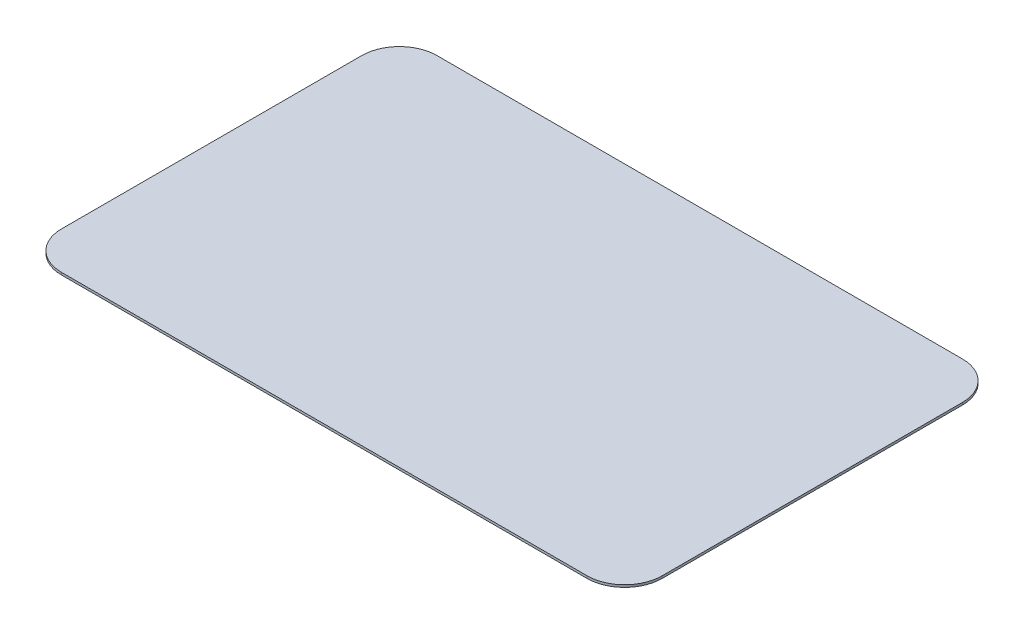
SolidWorks part; units mm, degrees
ref_plane "Front Plane" through (0, 0, 0) normal (0, 0, 1) x (1, 0, 0)
ref_plane "Top Plane" through (0, 0, 0) normal (0, 1, 0) x (1, 0, 0)
ref_plane "Right Plane" through (0, 0, 0) normal (1, 0, 0) x (0, 0, -1)
ref_plane "SheetPlane" through (0, 25.0193, 0) normal (0, 1, 0) x (1, 0, 0)
sketch "Sketch1" plane through (0, 25.0193, 0) normal (0, 1, 0) x (1, 0, 0)
  line L1 (-92.1192, -49.2656) -> (85.6808, -49.2656) construction
  line L2 (-104.8192, 65.0344) -> (-104.8192, -36.5656) construction
  line L3 (85.6808, 77.7344) -> (-92.1192, 77.7344) construction
  line L16 (98.3808, -36.5656) -> (98.3808, 65.0344)
  line L17 (-92.1192, -49.2656) -> (85.6808, -49.2656)
  line L18 (-104.8192, 65.0344) -> (-104.8192, -36.5656)
  line L19 (85.6808, 77.7344) -> (-92.1192, 77.7344)
  line L20 (98.3808, -36.5656) -> (98.3808, 65.0344) construction
  arc A0 (-92.1192, 77.7344) -> (-104.8192, 65.0344) centre (-92.1192, 65.0344) ccw construction
  arc A1 (-104.8192, -36.5656) -> (-92.1192, -49.2656) centre (-92.1192, -36.5656) ccw construction
  arc A2 (-92.1192, 77.7344) -> (-104.8192, 65.0344) centre (-92.1192, 65.0344) ccw
  arc A3 (85.6808, -49.2656) -> (98.3808, -36.5656) centre (85.6808, -36.5656) ccw construction
  arc A12 (85.6808, -49.2656) -> (98.3808, -36.5656) centre (85.6808, -36.5656) ccw
  arc A13 (98.3808, 65.0344) -> (85.6808, 77.7344) centre (85.6808, 65.0344) ccw construction
  arc A14 (98.3808, 65.0344) -> (85.6808, 77.7344) centre (85.6808, 65.0344) ccw
  arc A18 (-104.8192, -36.5656) -> (-92.1192, -49.2656) centre (-92.1192, -36.5656) ccw
extrude "MainBody" add sketch "Sketch1" along normal blind 0.7937
equation "\"SheetThickness\"= 0.03125in"
equation "\"D1@MainBody\" = \"SheetThickness\""
equation "\"SheetTolerance\"= 0.012in"
